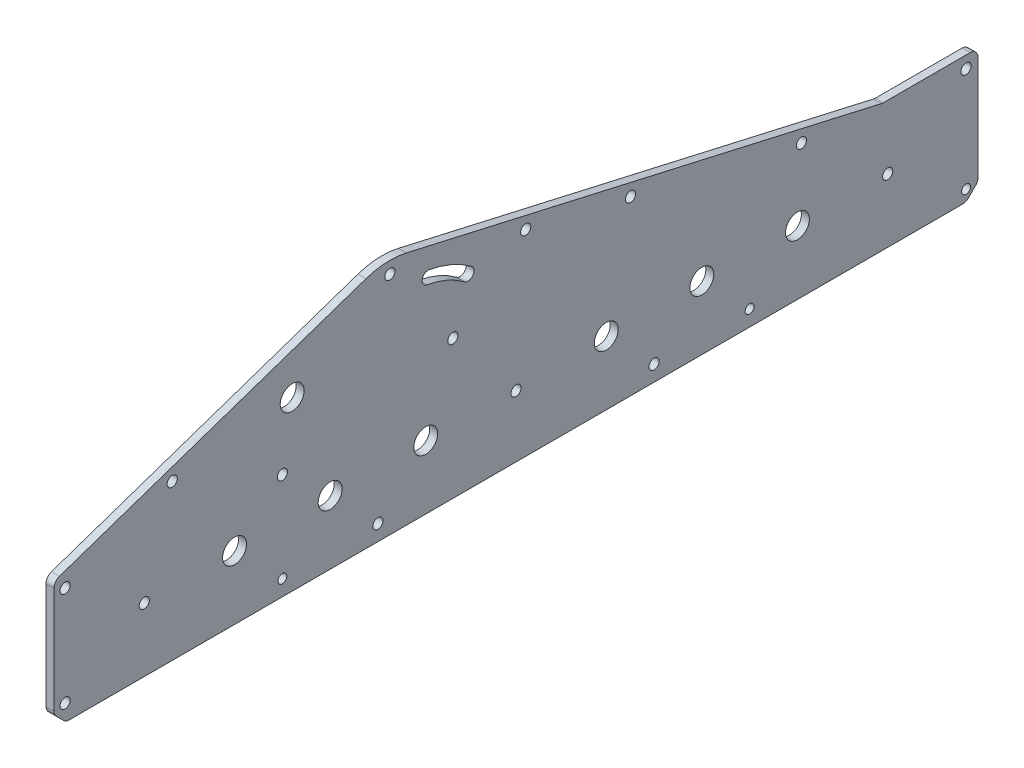
SolidWorks part; units mm, degrees
ref_plane "Front Plane" through (0, 0, 0) normal (0, 0, 1) x (1, 0, 0)
ref_plane "Top Plane" through (0, 0, 0) normal (0, 1, 0) x (1, 0, 0)
ref_plane "Right Plane" through (0, 0, 0) normal (1, 0, 0) x (0, 0, -1)
sketch "Sketch1" plane through (0, 0, 0) normal (1, 0, 0) x (0, 0, -1)
  line L0 (-184.15, 26.1937) -> (-59.8122, 68.5626)
  line L1 (-184.15, -24.6062) -> (184.15, -24.6062)
  line L2 (-184.15, -24.6062) -> (-184.15, 26.1937)
  line L3 (146.05, 26.1937) -> (184.15, 26.1937)
  line L4 (184.15, -24.6062) -> (184.15, 26.1937)
  line L9 (146.05, 26.1937) -> (-43.7083, 69.4049)
  arc A0 (-59.8122, 68.5626) -> (-43.7083, 69.4049) centre (-50.2741, 40.5715) cw
  arc A4 (-45.783, 38.8051) -> (-54.7652, 42.3379) centre (-50.2741, 40.5715) ccw construction
  arc A5 (-42.7051, 69.1579) -> (-57.8431, 69.1579) centre (-50.2741, 40.5715) ccw construction
  point P6 (0, -24.6062)
  point P9 (-48.0044, 57.6866)
  point P10 (-60.2023, 79.6782)
  point P15 (-43.522, 71.1312)
  dimension "D1" = 50.8
  dimension "D2" = 368.3
  dimension "D3" = 24.6062
  dimension "D5" = 38.1
extrude "Boss-Extrude1" add sketch "Sketch1" along normal blind 3.175
chamfer "Chamfer1" distance 4.7625 angle 45 2 edges at (1.5875, -24.6062, -184.15) (1.5875, -24.6062, 184.15)
fillet "Fillet1" radius 3.175 7 edges at (1.5875, -24.6062, -179.3875) (1.5875, -19.8437, -184.15) (1.5875, 26.1937, -184.15) (1.5875, -24.6062, 179.3875) (1.5875, -19.8437, 184.15) (1.5875, 26.1937, 184.15) (1.5875, 26.1937, -146.05)
sketch "Sketch4" plane through (3.175, 0, 0) normal (1, 0, 0) x (0, 0, -1)
  circle A0 centre (-137.0088, 37.226) radius 1.905 construction
  circle A2 centre (3.8736, 53.6853) radius 1.905 construction
  circle A3 centre (45.6663, 44.1684) radius 1.905 construction
  circle A4 centre (113.7728, 28.6594) radius 1.905 construction
  circle A5 centre (-25.1593, 30.6938) radius 2.032 construction
  circle A6 centre (-50.2741, 65.3805) radius 1.905 construction
  point P3 (0, 0)
  point P9 (55.0246, -18.3223)
  point P11 (-55.0246, -18.3223)
  point P13 (-179.705, 21.7487)
  point P15 (-179.705, -18.0026)
  point P17 (179.3875, 21.4312)
  point P19 (148.1579, 0.7938)
  point P21 (-148.1579, 0.7937)
  point P25 (-93.1246, 17.5943)
  point P28 (-137.0088, 37.226)
  point P32 (3.8736, 53.6853)
  point P34 (45.6663, 44.1684)
  point P36 (113.7728, 28.6594)
  point P54 (-25.1593, 30.6938)
  point P59 (-50.2741, 65.3805)
hole_wizard "#8 Clearance Hole1" positions "Sketch4" profile "Sketch5" hole size "#8" standard "ANSI Inch" end condition up to next
sketch "Sketch5" plane through (3.175, 0, 0) normal (0, 1, 0) x (0, 0, -1)
  line L0 (0, 0) -> (0, 3.175)
  line L1 (0, 3.175) -> (2.032, 3.175)
  line L2 (2.032, 3.175) -> (2.032, 0)
  line L5 (2.032, 0) -> (0, 0)
  line L11 (0, -6.35) -> (0, 107.95) construction
  dimension "Thru Hole Dia." = 4.064
  dimension "Thru Hole Depth" = 3.175
sketch "Sketch6" plane through (3.175, 0, 0) normal (1, 0, 0) x (0, 0, -1)
  point P0 (-93.1246, -18.3223)
  point P1 (93.1246, -18.3223)
  point P3 (179.3875, -20.1161)
hole_wizard "#8 Clearance Hole2" positions "Sketch6" profile "Sketch7" hole size "#8" standard "ANSI Inch" end condition up to next
sketch "Sketch7" plane through (3.175, -18.3223, 93.1246) normal (0, 1, 0) x (0, 0, -1)
  line L0 (0, 0) -> (0, 3.175)
  line L1 (0, 3.175) -> (1.778, 3.175)
  line L2 (1.778, 3.175) -> (1.778, 0)
  line L5 (1.778, 0) -> (0, 0)
  line L11 (0, -6.35) -> (0, 107.95) construction
  dimension "Thru Hole Dia." = 3.556
  dimension "Thru Hole Depth" = 3.175
sketch "Sketch8" plane through (3.175, 0, 0) normal (1, 0, 0) x (0, 0, -1)
  circle A0 centre (-89.211, 42.2593) radius 4.7625 construction
  point P0 (-112.1746, 0.7937)
  point P1 (-74.0746, 0.7938)
  point P3 (-35.9746, 0.7938)
  point P5 (35.9746, 0.7937)
  point P7 (74.0746, 0.7937)
  point P9 (112.1746, 0.7937)
  point P13 (-89.211, 42.2593)
hole_wizard "3/8 Clearance Hole1" positions "Sketch8" profile "Sketch9" hole size "3/8" standard "ANSI Inch" end condition up to next
sketch "Sketch9" plane through (3.175, 0.7937, 112.1746) normal (0, 1, 0) x (0, 0, -1)
  line L0 (0, 0) -> (0, 3.175)
  line L1 (0, 3.175) -> (4.7625, 3.175)
  line L2 (4.7625, 3.175) -> (4.7625, 0)
  line L5 (4.7625, 0) -> (0, 0)
  line L11 (0, -6.35) -> (0, 107.95) construction
  dimension "Thru Hole Dia." = 9.525
  dimension "Thru Hole Depth" = 3.175
sketch "Sketch10" plane through (3.175, 0, 0) normal (1, 0, 0) x (0, 0, -1)
  arc A0 (-34.5594, 59.0407) -> (-35.4169, 54.2915) centre (-34.9881, 56.6661) ccw construction
  arc A1 (-20.5473, 47.8719) -> (-35.4169, 54.2915) centre (-41.7582, 19.1724) ccw construction
  arc A2 (-20.5473, 47.8719) -> (-17.6789, 51.753) centre (-19.1131, 49.8125) ccw construction
  arc A3 (-17.6789, 51.753) -> (-34.5594, 59.0407) centre (-41.7582, 19.1724) ccw construction
  arc A4 (-34.5594, 59.0407) -> (-35.4169, 54.2915) centre (-34.9881, 56.6661) ccw
  arc A5 (-20.5473, 47.8719) -> (-35.4169, 54.2915) centre (-41.7582, 19.1724) ccw
  arc A6 (-20.5473, 47.8719) -> (-17.6789, 51.753) centre (-19.1131, 49.8125) ccw
  arc A7 (-17.6789, 51.753) -> (-34.5594, 59.0407) centre (-41.7582, 19.1724) ccw
extrude "Cut-Extrude1" cut sketch "Sketch10" against normal through all
